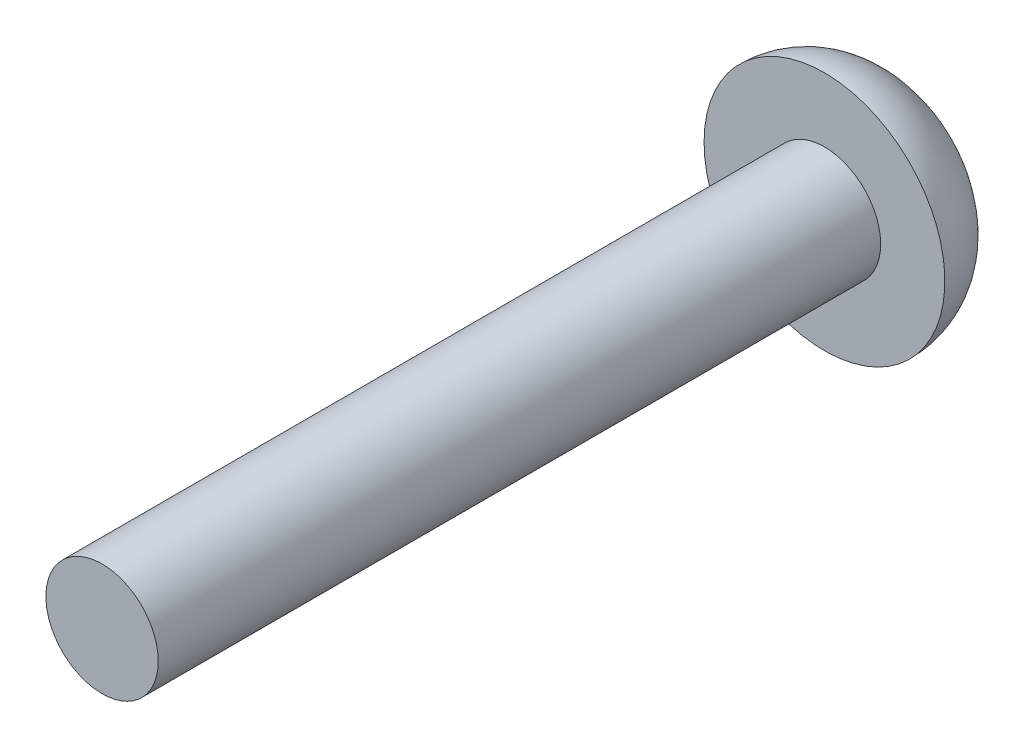
SolidWorks part; units mm, degrees
ref_plane "Plan de face" through (0, 0, 0) normal (0, 0, 1) x (1, 0, 0)
ref_plane "Plan de dessus" through (0, 0, 0) normal (0, 1, 0) x (1, 0, 0)
ref_plane "Plan de droite" through (0, 0, 0) normal (1, 0, 0) x (0, 0, -1)
sketch "Esquisse1" plane through (0, 0, 0) normal (0, 0, 1) x (1, 0, 0)
  circle A0 centre (0, 0) radius 1.4
  dimension "D1" = 2.8
extrude "Boss.-Extru.1" add sketch "Esquisse1" along normal blind 18
sketch "Esquisse2" plane through (0, 0, 0) normal (0, 0, -1) x (-1, 0, 0)
  circle A0 centre (0, 0) radius 3
  dimension "D1" = 6
extrude "Boss.-Extru.2" add sketch "Esquisse2" along normal blind 2
fillet "Congé2" radius 2 1 edges at (-3, 0, -2)
equation "\"L\"= 18"
equation "\"D1@Boss.-Extru.1\"=\"L\""
